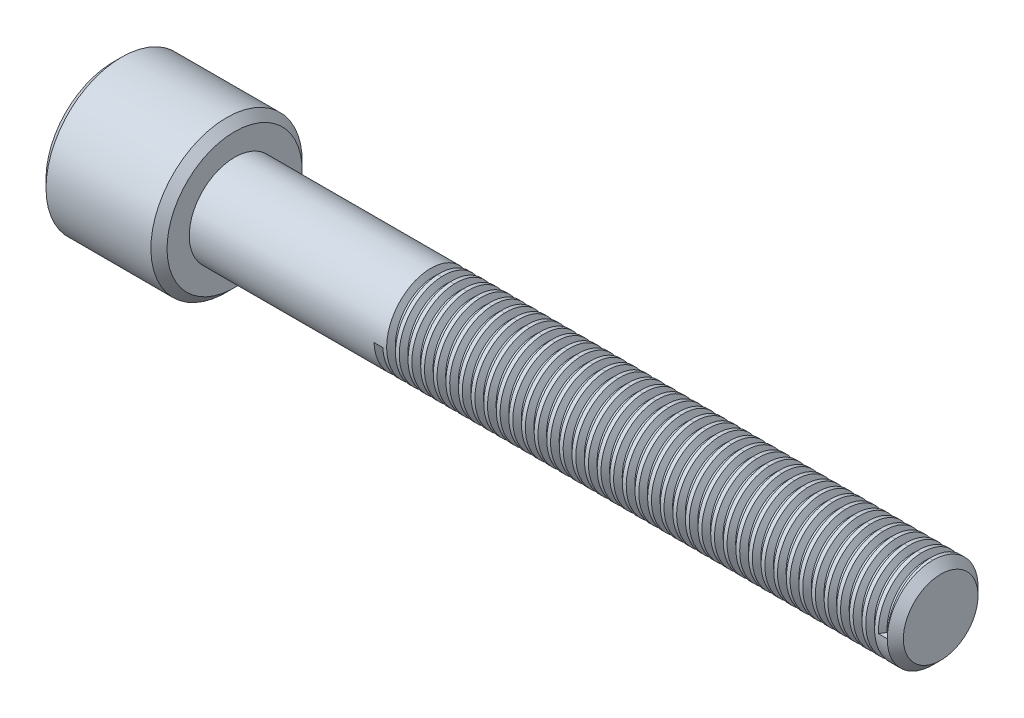
SolidWorks part; units mm, degrees
ref_plane "Front Plane" through (0, 0, 0) normal (0, 0, 1) x (1, 0, 0)
ref_plane "Top Plane" through (0, 0, 0) normal (0, 1, 0) x (1, 0, 0)
ref_plane "Right Plane" through (0, 0, 0) normal (1, 0, 0) x (0, 0, -1)
sketch "Sketch1" plane through (0, 0, 0) normal (0, 0, 1) x (1, 0, 0)
  line L0 (0, 0) -> (0, 7.5)
  line L1 (0, 7.5) -> (12, 7.5)
  line L2 (12, 7.5) -> (12, 4.5)
  line L3 (12, 4.5) -> (82, 4.5)
  line L4 (82, 4.5) -> (82, 0)
  line L5 (82, 0) -> (0, 0)
  dimension "D1" = 70
  dimension "D2" = 7.5
  dimension "D3" = 12
  dimension "D4" = 4.5
revolve "Revolve1" add sketch "Sketch1" angle 360 about L5
chamfer "Chamfer1" distance 0.8 angle 45 3 edges at (82, 4.5, 0) (12, 7.5, 0) (0, 7.5, 0)
sketch "Sketch2" plane through (0, 0, 0) normal (-1, 0, 0) x (0, 0, 1)
  line L7 (-3.25, 0) -> (-1.625, -2.8146)
  line L8 (-1.625, -2.8146) -> (1.625, -2.8146)
  line L9 (1.625, -2.8146) -> (3.25, 0)
  line L10 (3.25, 0) -> (1.625, 2.8146)
  line L11 (1.625, 2.8146) -> (-1.625, 2.8146)
  line L12 (-1.625, 2.8146) -> (-3.25, 0)
  circle A0 centre (0, 0) radius 3.25 construction
  dimension "D1" = 6.5
extrude "Cut-Extrude1" cut sketch "Sketch2" against normal blind 6
sketch "Sketch4" plane through (0, 0, 0) normal (0, 0, 1) x (1, 0, 0)
  line L1 (6, 0) -> (0, 0) construction
  line L2 (2.3094, 0) -> (0, 0)
  line L4 (0, 0) -> (0, 4)
  line L5 (0, 6.7) -> (0, -6.7) construction
  line L6 (0, 4) -> (2.3094, 0)
  line L9 (6, 0) -> (6, 4)
  line L18 (8.3094, 0) -> (6, 0)
  line L21 (6, 4) -> (8.3094, 0)
  dimension "D1" = 30
  dimension "D2" = 4
  dimension "D3" = 30
revolve "Cut-Revolve3" cut sketch "Sketch4" angle 360 about L2
thread "Thread1" pitch 1 method cut profile "Thread Profile1" start angle 0, offset 0, length 50, pitch 1.25, diameter 9
ref_plane "Plane1" through (81.2, 0, 4.5) normal (0, -1, 0) x (0, 0, 1)
sketch "Thread Profile1" plane through (81.2, 0, 4.5) normal (0, -1, 0) x (0, 0, 1)
  line L0 (0, 0) -> (0, 1) construction
  line L11 (0, 0) -> (0, 0.875)
  line L12 (0, 0.875) -> (-0.5413, 0.5625)
  line L13 (-0.5413, 0.5625) -> (-0.5413, 0.3125)
  line L15 (-0.5413, 0.3125) -> (0, 0)
  line L17 (-0.5413, 0.4375) -> (0, 0.4375) construction
  point P2 (0, 0)
  dimension "Pitch" = 1
  dimension "Profile_Angle" = 60
  dimension "Profile_Land" = 0.25
  dimension "Profile_Height" = 0.5413
